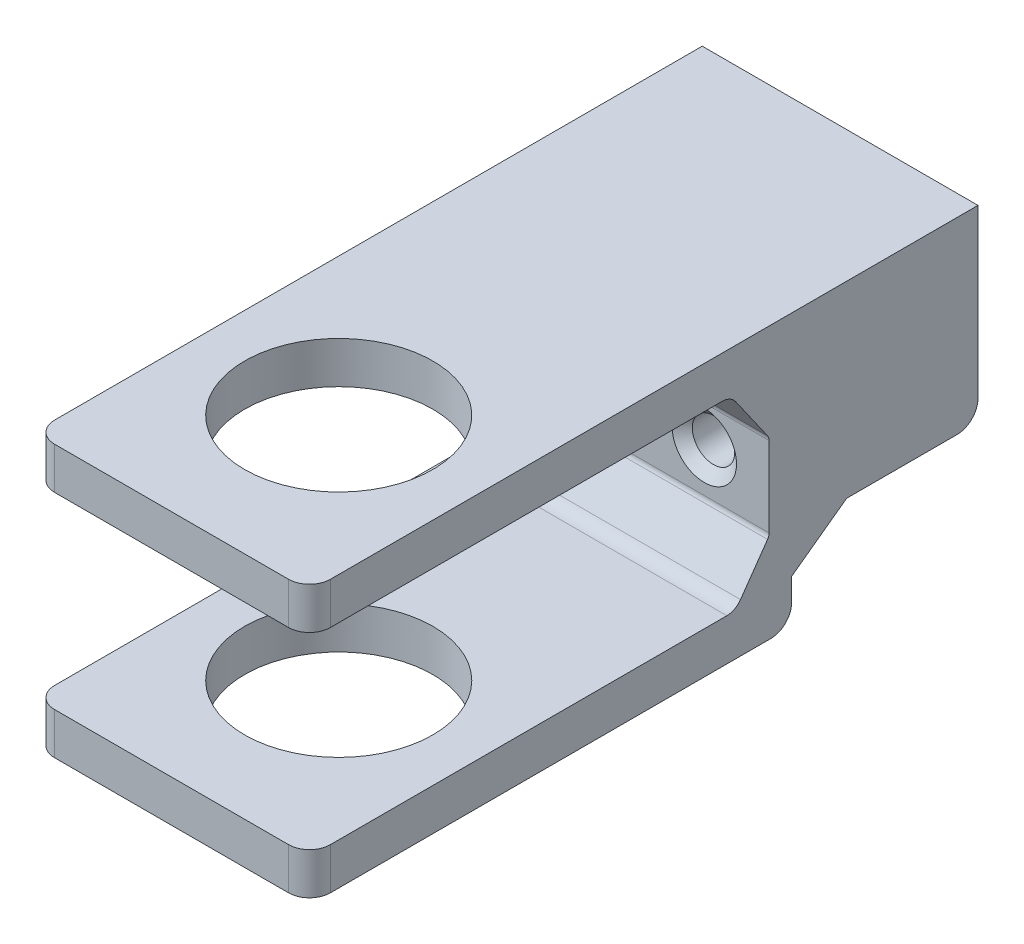
SolidWorks part; units mm, degrees
ref_plane "Front Plane" through (0, 0, 0) normal (0, 0, 1) x (1, 0, 0)
ref_plane "Top Plane" through (0, 0, 0) normal (0, 1, 0) x (1, 0, 0)
ref_plane "Right Plane" through (0, 0, 0) normal (1, 0, 0) x (0, 0, -1)
sketch "Sketch1" plane through (0, 0, 0) normal (0, 1, 0) x (1, 0, 0)
  line L1 (-20.955, -50.8) -> (20.955, -50.8)
  line L2 (-20.955, -50.8) -> (-20.955, 50.8)
  line L3 (-20.955, 50.8) -> (20.955, 50.8)
  line L4 (20.955, -50.8) -> (20.955, 50.8)
  line L5 (-20.955, -50.8) -> (20.955, 50.8) construction
  line L6 (-20.955, 50.8) -> (20.955, -50.8) construction
  point P0 (0, 0)
  dimension "D1" = 41.91
  dimension "D2" = 101.6
extrude "Boss-Extrude1" add sketch "Sketch1" along normal blind 41.275
sketch "Sketch13" plane through (-20.955, 0, 0) normal (-1, 0, 0) x (0, 0, 1)
  line L0 (-19.05, 26.6024) -> (-13.2225, 34.925)
  line L1 (-13.2225, 34.925) -> (50.8, 34.925)
  line L2 (-19.05, 26.6024) -> (-19.05, 13.6323)
  line L3 (-13.9509, 6.35) -> (50.8, 6.35)
  line L4 (-50.8, 0) -> (50.8, 0)
  line L5 (50.8, 0) -> (50.8, 41.275)
  line L6 (50.8, 41.275) -> (-50.8, 41.275)
  line L7 (-50.8, 41.275) -> (-50.8, 0)
  line L8 (-50.8, 0) -> (50.8, 0)
  line L9 (50.8, 0) -> (50.8, 41.275)
  line L10 (50.8, 41.275) -> (-50.8, 41.275)
  line L11 (-50.8, 41.275) -> (-50.8, 0)
  line L12 (50.8, 34.925) -> (50.8, 6.35)
  line L13 (-19.05, 13.6323) -> (-13.9509, 6.35)
  line M11 (50.8, 0) -> (50.8, 41.275)
  dimension "D2" = 6.35
  dimension "D3" = 31.75
  dimension "D4" = 6.35
  dimension "D5" = 10.16
  dimension "D6" = 125
  dimension "D7" = 8.89
  dimension "D8" = 64.0225
  dimension "D9" = 125
  dimension "D1" = 0
extrude "Cut-Extrude6" cut sketch "Sketch13" against normal through all contours L2 L13 L3 L1 L0 M11 region at (-20.955, 20.6073, 16.6003)
sketch "Sketch3" plane through (0, 41.275, 0) normal (0, 1, 0) x (1, 0, 0)
  line L1 (20.955, 50.8) -> (-20.955, 50.8) construction
  line L3 (2.7496, -20.6375) -> (-2.7496, -20.6375)
  line L4 (-2.7496, -20.6375) -> (-5.4993, -25.4)
  line L5 (-5.4993, -25.4) -> (-2.7496, -30.1625)
  line L6 (-2.7496, -30.1625) -> (2.7496, -30.1625)
  line L7 (2.7496, -30.1625) -> (5.4993, -25.4)
  line L8 (5.4993, -25.4) -> (2.7496, -20.6375)
  circle A0 centre (0, -25.4) radius 50.8
  circle A1 centre (0, -25.4) radius 4.7625 construction
  circle A2 centre (0, -25.4) radius 14.3002
  dimension "D1" = 101.6
  dimension "D2" = 25.4
  dimension "D3" = 9.525
  dimension "D4" = 28.6004
extrude "Cut-Extrude2" cut sketch "Sketch3" against normal through all contours L7 L8 L3 L4 L5 L6 | A2 L8 L7 L6 L5 L4 L3 region at (0, 41.275, 25.4) region at (-13.8957, 41.275, 25.4)
sketch "Sketch17" plane through (-20.955, 0, 0) normal (-1, 0, 0) x (0, 0, 1)
  line L0 (-30.8359, 12.7) -> (-22.479, 6.6084)
  line L11 (-50.8, 41.275) -> (-50.8, 0) construction
  line L16 (-50.8, 0) -> (-22.479, 0)
  line L17 (-50.8, 0) -> (-50.8, 12.7)
  line L18 (-50.8, 12.7) -> (-30.8359, 12.7)
  line L19 (-22.479, 0) -> (-22.479, 6.6084)
  line L20 (-50.8, 0) -> (50.8, 0) construction
  point P1 (-22.479, 6.6084)
  dimension "D1" = 28.321
  dimension "D2" = 12.7
  dimension "D3" = 10.3414
  dimension "D4" = 6.6084
extrude "Cut-Extrude7" cut sketch "Sketch17" against normal through all
sketch "Sketch4" plane through (0, 0, -50.8) normal (0, 0, -1) x (-1, 0, 0)
  line L0 (-20.955, 20.6375) -> (20.955, 20.6375) construction
  line L1 (-20.955, 41.275) -> (-20.955, 12.7) construction
  line L3 (11.1125, 20.6375) -> (-11.1125, 20.6375) construction
  line L4 (-20.955, 41.275) -> (20.955, 41.275) construction
  circle A0 centre (11.1125, 20.6375) radius 3.2258
  circle A1 centre (-11.1125, 20.6375) radius 3.2258
  point P10 (0, 20.6375)
  point P12 (0, 20.6375)
  dimension "D1" = 6.4516
  dimension "D2" = 22.225
  dimension "D3" = 20.6375
  dimension "D4" = 41.91
extrude "Cut-Extrude3" cut sketch "Sketch4" against normal through all
fillet "Fillet2" radius 3.175 6 edges at (-20.955, 3.175, 50.8) (20.955, 3.175, 50.8) (-20.955, 38.1, 50.8) (20.955, 38.1, 50.8) (0, 12.7, -50.8) (0, 0, -22.479)
hole_wizard "CSK for #10 Flat Head Machine Screw (100)4" positions "Sketch14" profile "Sketch15" countersink size "#10" standard "ANSI Inch"
sketch "Sketch14" plane through (0, 0, -19.05) normal (0, 0, 1) x (1, 0, 0)
  point P0 (-11.1125, 20.6375)
  point P3 (11.1125, 20.6375)
sketch "Sketch15" plane through (-11.1125, 20.6375, -19.05) normal (1, 0, 0) x (0, -1, 0)
  line L0 (0, 0) -> (0, 33.4364)
  line L1 (0, 33.4364) -> (2.8067, 31.75)
  line L2 (2.8067, 31.75) -> (2.8067, 1.7477)
  line L3 (2.8067, 1.7477) -> (4.8895, 0)
  line L5 (4.8895, 0) -> (0, 0)
  line L6 (-2.8067, 1.7477) -> (-4.8895, 0) construction
  line L10 (0, 33.4364) -> (-2.8067, 31.75) construction
  line L11 (0, -6.35) -> (0, 107.95) construction
  dimension "Hole Dia." = 5.6134
  dimension "Hole Depth" = 31.75
  dimension "Near C'Sink Dia." = 9.779
  dimension "Near C'Sink Angle" = 100
  dimension "Drill Angle" = 118
fillet "Fillet3" radius 2.54 2 edges at (0, 6.35, -13.9509) (0, 34.925, -13.2225)
fillet "Fillet4" radius 1.27 2 edges at (0, 13.6323, -19.05) (0, 26.6024, -19.05)
